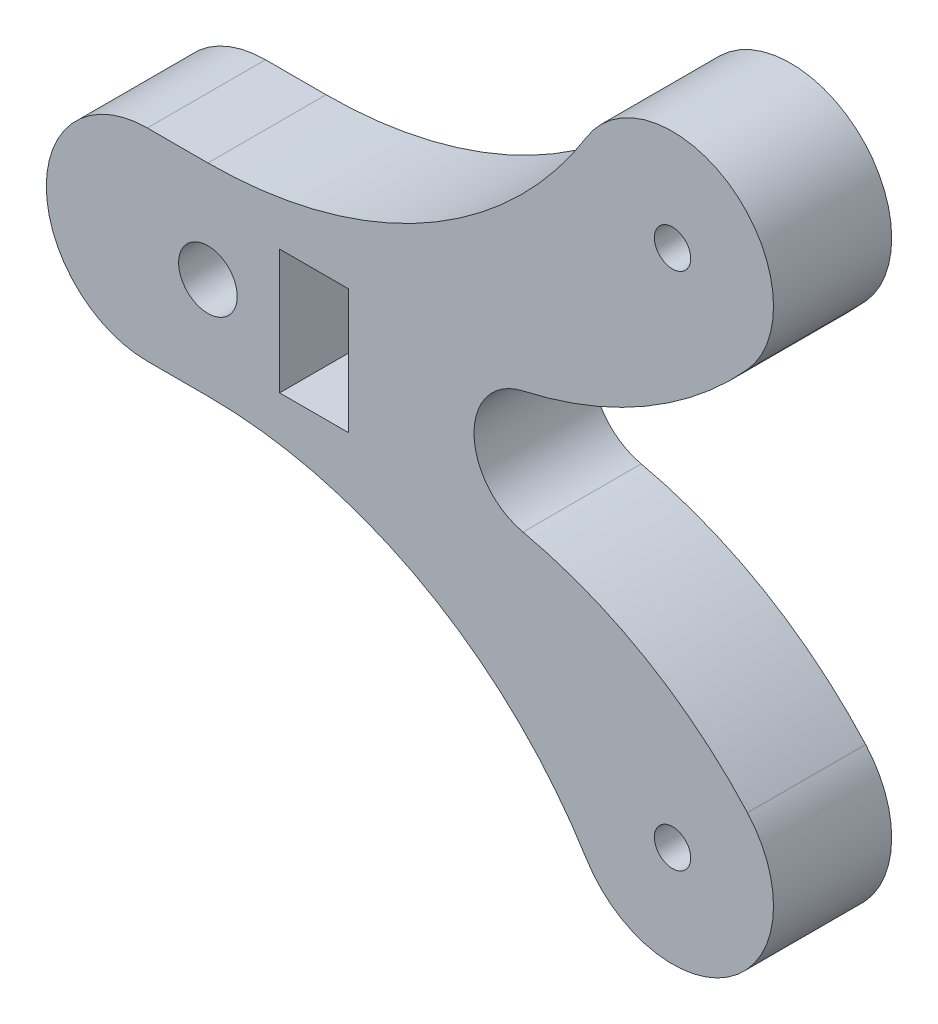
SolidWorks part; units mm, degrees
material "Acrylic (Medium-high impact)"
ref_plane "Front Plane" through (0, 0, 0) normal (0, 0, 1) x (1, 0, 0)
ref_plane "Top Plane" through (0, 0, 0) normal (0, 1, 0) x (1, 0, 0)
ref_plane "Right Plane" through (0, 0, 0) normal (1, 0, 0) x (0, 0, -1)
sketch "Sketch1" plane through (0, 0, 0) normal (0, 0, 1) x (1, 0, 0)
  line L0 (587.4699, 435.3658) -> (583.9197, 435.3658) construction
  line L1 (594.1695, 438.4483) -> (594.1695, 432.2833) construction
  line L2 (592.4695, 438.4483) -> (595.8695, 438.4483)
  line L3 (595.8695, 438.4483) -> (595.8695, 432.2833)
  line L4 (595.8695, 432.2833) -> (592.4695, 432.2833)
  line L5 (592.4695, 432.2833) -> (592.4695, 438.4483)
  line L6 (588.9197, 433.916) -> (588.9197, 430.3658) construction
  line L7 (588.9197, 436.8156) -> (588.9197, 440.3658) construction
  line L8 (592.4695, 435.3658) -> (595.8695, 435.3658) construction
  line L9 (588.9197, 440.3658) -> (585.9197, 440.3658)
  line L10 (611.9197, 448.2184) -> (611.9197, 422.5133) construction
  line L11 (611.9197, 422.5133) -> (611.9197, 425.8485) construction
  line L12 (602.0913, -564.4599) -> (602.0913, 49435.5401) construction
  line L13 (611.9197, 422.5133) -> (611.9197, 419.178) construction
  line L14 (588.9197, 430.3658) -> (585.9197, 430.3658)
  line L16 (611.9197, 448.2184) -> (611.9197, 451.5536) construction
  line L17 (611.9197, 448.2184) -> (611.9197, 444.8831) construction
  line L20 (606.9306, 435.3658) -> (50606.9306, 435.3658) construction
  circle A0 centre (611.9197, 448.2184) radius 0.9
  circle A1 centre (611.9197, 422.5133) radius 0.9
  circle A2 centre (588.9197, 435.3658) radius 1.4498
  arc A3 (585.9197, 440.3658) -> (585.9197, 430.3658) centre (585.9197, 435.3658) ccw
  arc A4 (607.6499, 450.82) -> (615.6304, 444.8672) centre (611.9197, 448.2184) cw
  arc A5 (588.9197, 440.3658) -> (607.6499, 450.82) centre (588.9197, 462.3718) ccw
  arc A6 (604.518, 438.3918) -> (604.518, 432.3398) centre (605.1913, 435.3658) ccw
  arc A7 (604.518, 438.3918) -> (615.6304, 444.8672) centre (599.9199, 459.0555) ccw
  arc A8 (604.518, 432.3398) -> (615.6304, 425.8645) centre (599.9199, 411.6761) cw
  arc A9 (607.6499, 419.9116) -> (615.6304, 425.8645) centre (611.9197, 422.5133) ccw
  arc A10 (588.9197, 430.3658) -> (607.6499, 419.9116) centre (588.9197, 408.3598) cw
  point P33 (602.0913, 435.3658)
  point P35 (590.3695, 435.3658)
  dimension "D1" = 2.1
  dimension "D4" = 1.8
  dimension "D8" = 3.1
  dimension "D10" = 5
  dimension "D11" = 3
  dimension "D2" = 23
  dimension "D3" = 10
  dimension "D5" = 12.8525
  dimension "D6" = 6.165
  dimension "D7" = 3.4
  dimension "D9" = 6.2218
  dimension "D12" = 18.7302
  dimension "D13" = 11.1125
extrude "Boss-Extrude1" add sketch "Sketch1" along normal blind 5.85
